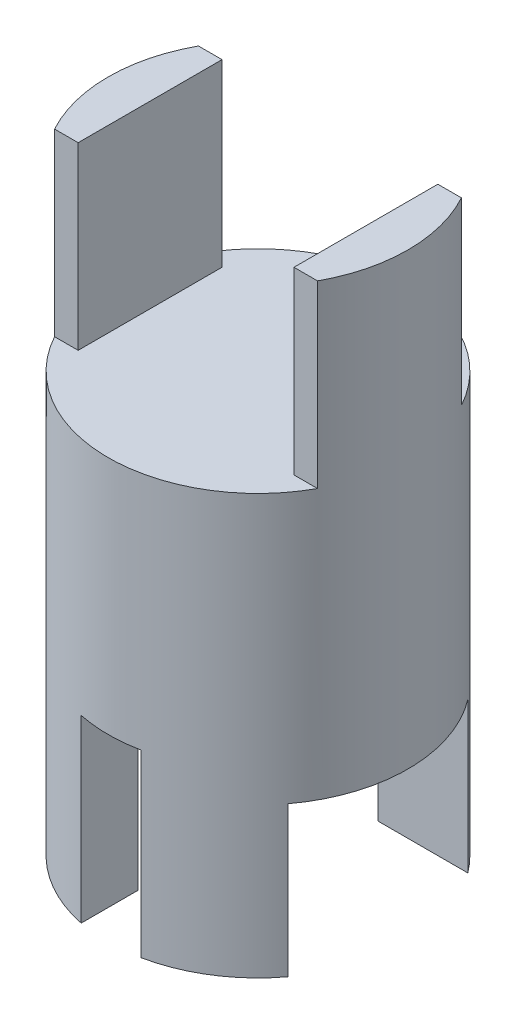
SolidWorks part; units mm, degrees
ref_plane "Front Plane" through (0, 0, 0) normal (1, 0, 0) x (0, 1, 0)
ref_plane "Top Plane" through (0, 0, 0) normal (0, 0, 1) x (0, 1, 0)
ref_plane "Right Plane" through (0, 0, 0) normal (0, 1, 0) x (-1, 0, 0)
sketch "Sketch1" plane through (0, 0, 0) normal (0, 1, 0) x (-1, 0, 0)
  circle A0 centre (0, 0) radius 25
  dimension "D1" = 50
extrude "Boss-Extrude1" add sketch "Sketch1" against normal blind 25
sketch "Sketch2" plane through (0, 0, 0) normal (1, 0, 0) x (0, 1, 0)
  line L0 (-25, 25) -> (-25, -25) construction
  line L1 (-25, 15) -> (0, 15)
  line L2 (-25, 15) -> (-25, -15)
  line L3 (-25, -15) -> (0, -15)
  line L4 (0, 15) -> (0, -15)
  point P6 (0, 0)
  dimension "D1" = 30
  dimension "D2" = 25
extrude "Boss-Extrude2" add sketch "Sketch1<2>" along normal blind 75
sketch "Sketch1<2>" plane through (0, 0, 0) normal (0, 1, 0) x (-1, 0, 0) same geometry as "Sketch1"
extrude "Cut-Extrude1" cut sketch "Sketch2" against normal through all both and the other way through all
sketch "Sketch5" plane through (0, 0, 0) normal (1, 0, 0) x (0, 1, 0)
  line L0 (0, 0) -> (82.6251, 0) construction
  line L1 (75, 25) -> (45, 25)
  line L2 (75, 25) -> (75, 12)
  line L3 (75, 12) -> (45, 12)
  line L4 (45, 25) -> (45, 12)
  line L5 (45, -25) -> (45, -12)
  line L6 (75, -25) -> (45, -25)
  line L7 (75, -25) -> (75, -12)
  line L8 (75, -12) -> (45, -12)
  dimension "D1" = 30
  dimension "D2" = 13
extrude "Cut-Extrude2" cut sketch "Sketch5" against normal through all both and the other way through all
sketch "Sketch6" plane through (0, 0, 0) normal (0, 0, 1) x (0, 1, 0)
  line L0 (-25, 20) -> (-25, -20) construction
  line L1 (-25, 5) -> (5, 5)
  line L2 (-25, 5) -> (-25, -5)
  line L3 (-25, -5) -> (5, -5)
  line L4 (5, 5) -> (5, -5)
  point P7 (-25, 0)
  dimension "D1" = 10
  dimension "D2" = 30
extrude "Cut-Extrude3" cut sketch "Sketch6" against normal through all both and the other way through all
sketch "Sketch8" plane through (0, 0, 0) normal (0, 0, 1) x (0, 1, 0)
  line L0 (45, 21.9317) -> (45, -21.9317) construction
  line L1 (45, 18) -> (75, 18)
  line L2 (45, 18) -> (45, -18)
  line L3 (45, -18) -> (75, -18)
  line L4 (75, 18) -> (75, -18)
  line L5 (75, -21.9317) -> (75, 21.9317) construction
  point P8 (45, 0)
  dimension "D1" = 36
extrude "Cut-Extrude4" cut sketch "Sketch8" against normal through all both and the other way through all
